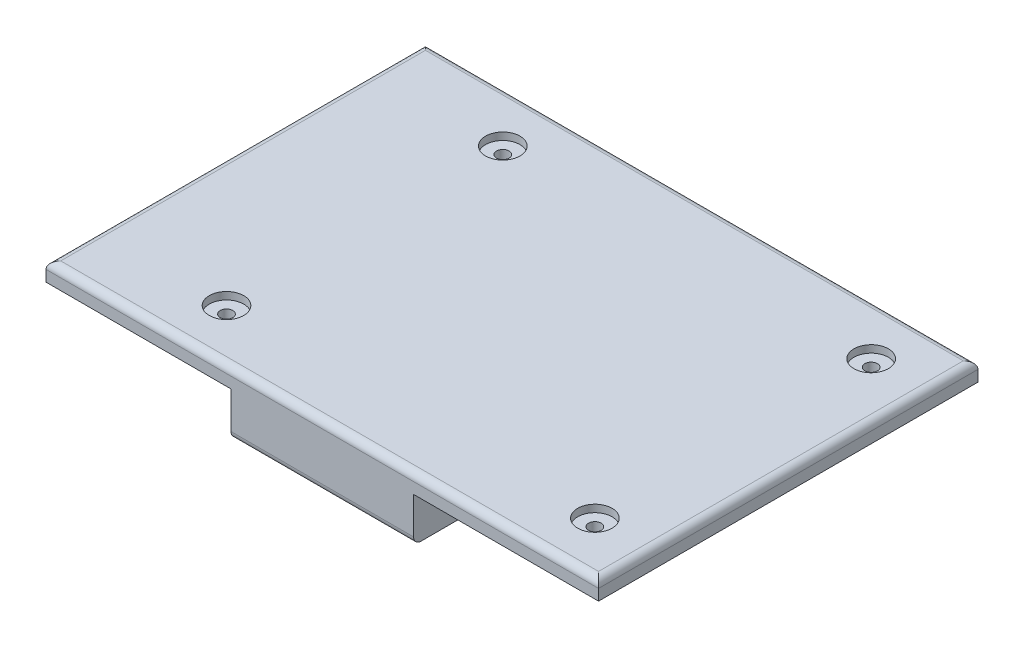
SolidWorks part; units mm, degrees
ref_plane "Front Plane" through (0, 0, 0) normal (0, 0, 1) x (1, 0, 0)
ref_plane "Top Plane" through (0, 0, 0) normal (0, 1, 0) x (1, 0, 0)
ref_plane "Right Plane" through (0, 0, 0) normal (1, 0, 0) x (0, 0, -1)
sketch "Sketch1" plane through (0, 0, 0) normal (0, 1, 0) x (1, 0, 0)
  line L1 (0, 0) -> (150, 0)
  line L2 (0, 0) -> (0, 103)
  line L3 (0, 103) -> (150, 103)
  line L4 (150, 0) -> (150, 103)
  dimension "D1" = 150
  dimension "D2" = 103
extrude "Boss-Extrude1" add sketch "Sketch1" along normal blind 5
sketch "Sketch4" plane through (0, 0, 0) normal (0, -1, 0) x (1, 0, 0)
  line L24 (145.1, -83) -> (145.1, -20)
  line L25 (144, -18.9) -> (6, -18.9)
  line L26 (4.9, -20) -> (4.9, -83)
  line L27 (6, -84.1) -> (144, -84.1)
  line L28 (145.1, -83) -> (145.1, -20)
  line L29 (144, -18.9) -> (6, -18.9)
  line L30 (4.9, -20) -> (4.9, -83)
  line L31 (6, -84.1) -> (144, -84.1)
  arc A20 (144, -84.1) -> (145.1, -83) centre (144, -83) ccw
  arc A21 (145.1, -20) -> (144, -18.9) centre (144, -20) ccw
  arc A22 (6, -18.9) -> (4.9, -20) centre (6, -20) ccw
  arc A23 (4.9, -83) -> (6, -84.1) centre (6, -83) ccw
  arc A24 (144, -84.1) -> (145.1, -83) centre (144, -83) ccw
  arc A25 (145.1, -20) -> (144, -18.9) centre (144, -20) ccw
  arc A26 (6, -18.9) -> (4.9, -20) centre (6, -20) ccw
  arc A27 (4.9, -83) -> (6, -84.1) centre (6, -83) ccw
  dimension "D1" = 0.15
sketch "Sketch2" plane through (0, 0, 0) normal (0, -1, 0) x (1, 0, 0)
  line L0 (0, 0) -> (150, 0) construction
  line L1 (50.2, 0) -> (99.8, 0)
  line L2 (50.2, 0) -> (50.2, -13.8)
  line L3 (50.2, -13.8) -> (99.8, -13.8)
  line L4 (99.8, 0) -> (99.8, -13.8)
  line L5 (0, -103) -> (0, 0) construction
  line L6 (150, 0) -> (150, -103) construction
  line L7 (0, -51.5) -> (150, -51.5) construction
  line L8 (99.8, -103) -> (99.8, -89.2)
  line L9 (50.2, -89.2) -> (99.8, -89.2)
  line L10 (50.2, -103) -> (50.2, -89.2)
  line L11 (50.2, -103) -> (99.8, -103)
  dimension "D1" = 50.2
  dimension "D2" = 50.2
  dimension "D3" = 13.8
extrude "Boss-Extrude2" add sketch "Sketch2" along normal blind 12
extrude "Cut-Extrude1" cut sketch "Sketch4" against normal blind 1.2
fillet "Fillet1" radius 2 8 edges at (75, -12, -89.2) (75, -12, -103) (75, -12, -13.8) (75, -12, 0) (150, 5, -51.5) (75, 5, -103) (75, 5, 0) (0, 5, -51.5)
hole_wizard "CBORE for M3 Hex Head Cap Screw1" positions "Sketch6" profile "Sketch5" counterbore size "M3" standard "ISO" end condition through all
sketch "Sketch6" plane through (0, 5, 0) normal (0, 1, 0) x (1, 0, 0)
  point P0 (35, 89)
  point P3 (35, 14)
  point P6 (135, 14)
  point P9 (135, 89)
sketch "Sketch5" plane through (35, 5, -89) normal (1, 0, 0) x (0, 0, 1)
  line L0 (0, 0) -> (0, 17)
  line L1 (0, 17) -> (1.7, 17)
  line L3 (1.7, 17) -> (1.7, 2)
  line L4 (1.7, 2) -> (4.6755, 2)
  line L5 (4.6755, 2) -> (4.6755, 0)
  line L7 (4.6755, 0) -> (0, 0)
  line L11 (0, -6.35) -> (0, 107.95) construction
  dimension "Thru Hole Dia." = 3.4
  dimension "Thru Hole Depth" = 17
  dimension "C'Bore Dia." = 9.351
  dimension "C'Bore Depth" = 2
